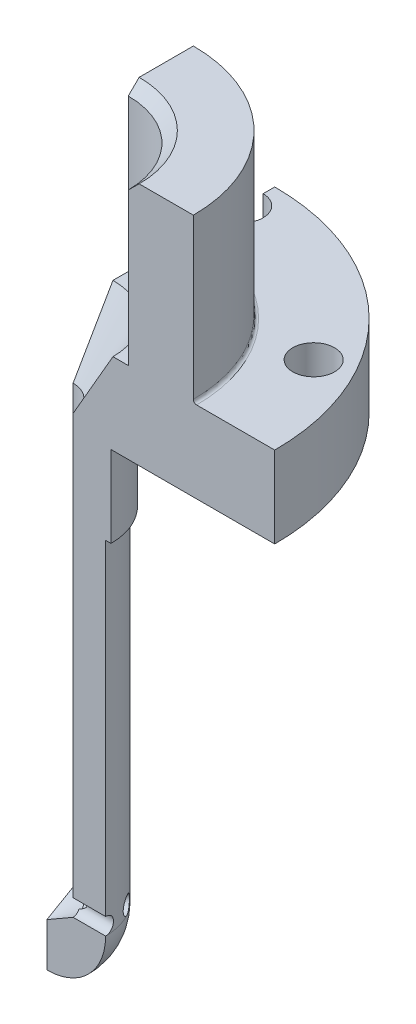
SolidWorks part; units mm, degrees
note: '?' marks a value the reader was unsure of.
ref_plane "Front Plane" through (0, 0, 0) normal (0, 0, 1) x (1, 0, 0)
ref_plane "Top Plane" through (0, 0, 0) normal (0, 1, 0) x (1, 0, 0)
ref_plane "Right Plane" through (0, 0, 0) normal (1, 0, 0) x (0, 0, -1)
sketch "Sketch1" plane through (0, 0, 0) normal (0, 0, 1) x (1, 0, 0)
  line L0 (-4.5847, -3.6623) -> (-2.0447, -3.6623)
  line L1 (0, 8.2157) -> (0, -2.0672) construction
  line L2 (-4.5847, 23.0788) -> (-2.0447, 23.0788)
  line L3 (-4.5847, -3.6623) -> (-4.5847, 23.0788)
  line L7 (-2.0447, 23.0788) -> (-2.0447, -3.6623)
  dimension "D2" = 4.5847
  dimension "D3" = 2.0447
  dimension "D4" = 26.7411
revolve "Revolve2" add sketch "Sketch1" angle 360 about L1
ref_plane "Plane1" through (-4.5847, 0, 0) normal (-1, 0, 0) x (0, 0, 1)
ref_axis "Axis2" through (0, -3.6623, 0) along (0, 1, 0)?
ref_plane "Plane2" through (0, 23.0788, 0) normal (0, -1, 0) x (-1, 0, 0)
sketch "Sketch3" plane through (0, 23.0788, 0) normal (0, -1, 0) x (-1, 0, 0)
  circle A0 centre (0, 0) radius 2.0447 construction
  circle A1 centre (0, 0) radius 4.5847 construction
  circle A2 centre (0, 0) radius 2.0447
  circle A3 centre (0, 0) radius 4.5847
extrude "Boss-Extrude1" add sketch "Sketch3" against normal blind 6.35
ref_plane "Plane3" through (0, 29.4288, 0) normal (0, 1, 0) x (1, 0, 0)
sketch "Sketch4" plane through (0, 29.4288, 0) normal (0, 1, 0) x (1, 0, 0)
  circle A0 centre (0, 0) radius 17.78
  circle A1 centre (0, 0) radius 2.0447
  dimension "D2" = 17.78
  dimension "D1" = 4.0894
extrude "Boss-Extrude2" add sketch "Sketch4" along normal blind 6.35
sketch "Sketch11" plane through (0, 35.7788, 0) normal (0, 1, 0) x (1, 0, 0)
  line L0 (0, 0) -> (0, -15.24) construction
  circle A0 centre (0, -15.24) radius 1.6319
  circle A1 centre (0, 0) radius 15.24 construction
  dimension "D2" = 3.2639
extrude "Cut-Extrude2" cut sketch "Sketch11" against normal up to next
ref_axis "Axis1" through (0, -3.6623, 0) along (0, 1, 0)?
pattern_circular "CirPattern2" count 6 over 360 about axis through (0, 0, 0) along (0, 1, 0) of "Cut-Extrude2"
chamfer "Chamfer1" distance 3.1128 angle 60 1 edges at (0, 35.7788, 2.0447)
sketch "Sketch13" plane through (0, 35.7788, 0) normal (0, 1, 0) x (1, 0, 0)
  circle A0 centre (0, 0) radius 6.35
  circle A1 centre (0, 0) radius 11.43
extrude "Boss-Extrude4" add sketch "Sketch13" along normal blind 12.7
fillet "Fillet4" radius 0.254 1 edges at (0, 35.7788, 11.43)
chamfer "Chamfer2" distance 0.8517 distance2 0.8395 1 edges at (0, 48.4788, 6.35)
sketch "Sketch14" plane through (0, 35.7788, 0) normal (0, 1, 0) x (1, 0, 0)
  circle A0 centre (-13.1982, -7.62) radius 2.794
sketch "Sketch15" plane through (0, 29.4288, 0) normal (0, -1, 0) x (1, 0, 0)
  circle A0 centre (0, 0) radius 5
  circle A1 centre (0, 0) radius 3.556
extrude "Boss-Extrude5" add sketch "Sketch15" along normal blind 6.35
sketch "Sketch18" plane through (0, -3.6623, 0) normal (0, -1, 0) x (1, 0, 0)
  circle A0 centre (0, 0) radius 4.318
sketch "Sketch19" plane through (0, 0, 0) normal (0, 0, 1) x (1, 0, 0)
  line L0 (0, -3.6623) -> (-4.5847, -3.6623)
  line L1 (-4.318, -3.6623) -> (4.318, -3.6623) construction
  line L2 (0, -3.6623) -> (0, -8.247)
  arc A0 (-4.5847, -3.6623) -> (0, -8.247) centre (0, -3.6623) ccw
  dimension "D2" = 4.5847
  dimension "D1" = 4.5847
ref_axis "Axis3" through (0, -3.6623, 0) along (0, -1, 0)
revolve "Revolve4" add sketch "Sketch19" angle 360 about axis through (0, -3.6623, 0) along (0, -1, 0)
sketch "Sketch20" plane through (-4.5847, 0, 0) normal (-1, 0, 0) x (0, 0, 1)
  line L1 (0, -3.6623) -> (0, -8.247) construction
  line L2 (-4.318, -3.6623) -> (4.318, -3.6623) construction
  circle A0 centre (0, -3.0019) radius 0.6604
  dimension "D2" = 1.3208
  dimension "D1" = 0.6604
extrude "Cut-Extrude3" cut sketch "Sketch20" against normal up to next
pattern_circular "CirPattern3" count 12 over 360 about axis through (0, -3.6623, 0) along (0, -1, 0) of "Cut-Extrude3"
sketch "Sketch21" plane through (0, 0, 0) normal (0, 0, 1) x (1, 0, 0)
  line L0 (0, -3.6623) -> (0, -4.8429)
  line L1 (-4.318, -3.6623) -> (4.318, -3.6623) construction
  line L5 (0, -3.6623) -> (-2.0447, -3.6623)
  line L6 (-2.0447, -3.6623) -> (0, -4.8429)
  spline S0 degree 2 poles (-1.975, -3.397) (-2.0011, -3.5274) (-2.0447, -3.6623) knots 0.746353 0.746353 0.746353 1 1 1 weights 0.00237 0.002538 0.002705 construction
  dimension "D1" = 30
revolve "Cut-Revolve4" cut sketch "Sketch21" angle 360 about axis through (0, -3.6623, 0) along (0, -1, 0)
sketch "Sketch22" plane through (0, 48.4788, 0) normal (0, 1, 0) x (1, 0, 0)
  line L0 (0, 0) -> (0, 19.8928)
  line L1 (0, 19.8928) -> (-23.5228, 19.8928)
  line L2 (-23.5228, 19.8928) -> (-23.5228, -23.8862)
  line L3 (-23.5228, -23.8862) -> (22.702, -23.8862)
  line L4 (22.702, -23.8862) -> (22.702, 0)
  line L5 (22.702, 0) -> (0, 0)
extrude "Cut-Extrude4" cut sketch "Sketch22" against normal through all
equation "\"ManifoldThickness\" = 0.25"
equation "\"D1@Boss-Extrude1\"=\"ManifoldThickness\""
equation "\"SkipDistance\"= \"OD\"'equal to pintle OD"
equation "\"OD\" = \"ID\" + 2 * 0.1'Inner diameter plus wall thickness"
equation "\"AnnulusLength\"= 0.3084"
equation "\"ManifoldChamberThickness\"= 0.3314"
equation "\"D4@Sketch1\"=\"SkipDistance\"+\"AnnulusLength\"+\"ManifoldChamberThickness\"+\"HoleHeight\""
equation "\"HoleHeight\"= 0.052"
equation "\"D2@Sketch1\"=\"OD\"/2"
equation "\"IR\"= 0.1610 / 2"
equation "\"D3@Sketch1\" = \"IR\""
equation "\"ID\"= \"IR\" * 2"
equation "\"440loose\"= 0.1285"
equation "\"D2@Sketch11\"=\"440loose\""
equation "\"ManifoldPlateThickness\"= 0.25"
equation "\"WeldHeight\"= 0.035"
equation "\"HoleFromEnd\"= \"HoleHeight\" / 2"
equation "\"D1@Sketch20\"=\"HoleFromEnd\""
equation "\"D2@Sketch20\"=\"HoleHeight\""
equation "\"D1@Sketch19\"=\"OD\"/2"
equation "\"D1@Sketch4\"=\"ID\""
